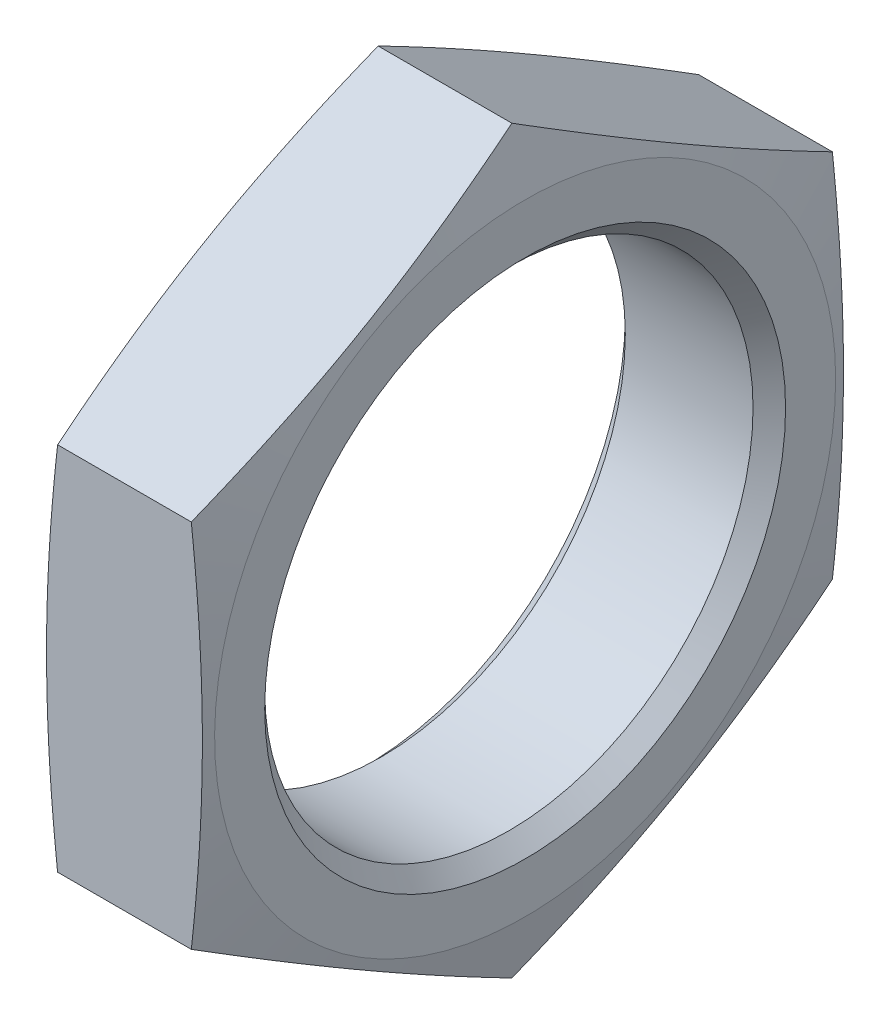
SolidWorks part; units mm, degrees
ref_plane "前视基准面" through (0, 0, 0) normal (0, 0, 1) x (1, 0, 0)
ref_plane "上视基准面" through (0, 0, 0) normal (0, 1, 0) x (1, 0, 0)
ref_plane "右视基准面" through (0, 0, 0) normal (1, 0, 0) x (0, 0, -1)
sketch "草图1" plane through (0, 0, 0) normal (0, 0, 1) x (1, 0, 0)
  line L0 (0, -15.5) -> (3.5, -31.2)
  line L1 (3.5, -31.2) -> (4.5, -31.2)
  line L2 (4.5, -31.2) -> (8, -15.5)
  line L3 (8, -15.5) -> (8, -13)
  line L4 (8, -13) -> (7.188, -12.188)
  line L5 (7.188, -12.188) -> (0.812, -12.188)
  line L6 (0.812, -12.188) -> (0, -13)
  line L7 (0, -13) -> (0, -15.5)
  line L8 (0, 0) -> (8, 0) construction
revolve "旋转1" add sketch "草图1" angle 360 about L8 reverse direction yes
cosmetic thread "装饰螺纹线1" parameters "D1"=8, "D2"=26
sketch "草图2" plane through (0, 0, 0) normal (1, 0, 0) x (0, 0, -1)
  line L0 (-16, 9.2376) -> (-16, -9.2376)
  line L1 (-16, -9.2376) -> (0, -18.4752)
  line L2 (0, -18.4752) -> (16, -9.2376)
  line L3 (16, -9.2376) -> (16, 9.2376)
  line L4 (16, 9.2376) -> (0, 18.4752)
  line L5 (0, 18.4752) -> (-16, 9.2376)
  circle A0 centre (0, 0) radius 48
extrude "切除-拉伸1" cut sketch "草图2" along normal blind 8
ref_plane "For_front cover XY" through (0, 0, 0) normal (1, 0, 0) x (0, 0, -1)
ref_plane "For_front cover XZ" through (0, 0, 0) normal (0, -1, 0) x (-1, 0, 0)
ref_plane "For_front cover YZ" through (0, 0, 0) normal (0, 0, -1) x (-1, 0, 0)
ref_axis "For_front cover X" through (0, 0, 80.9) along (0, 0, -1)
ref_axis "For_front cover Y" through (0, -50, 0) along (0, 1, 0)
ref_axis "For_front cover Z" through (80.9, 0, 0) along (-1, 0, 0)
sketch3d "For_front cover"
  point P0 (0, 0, 0)
